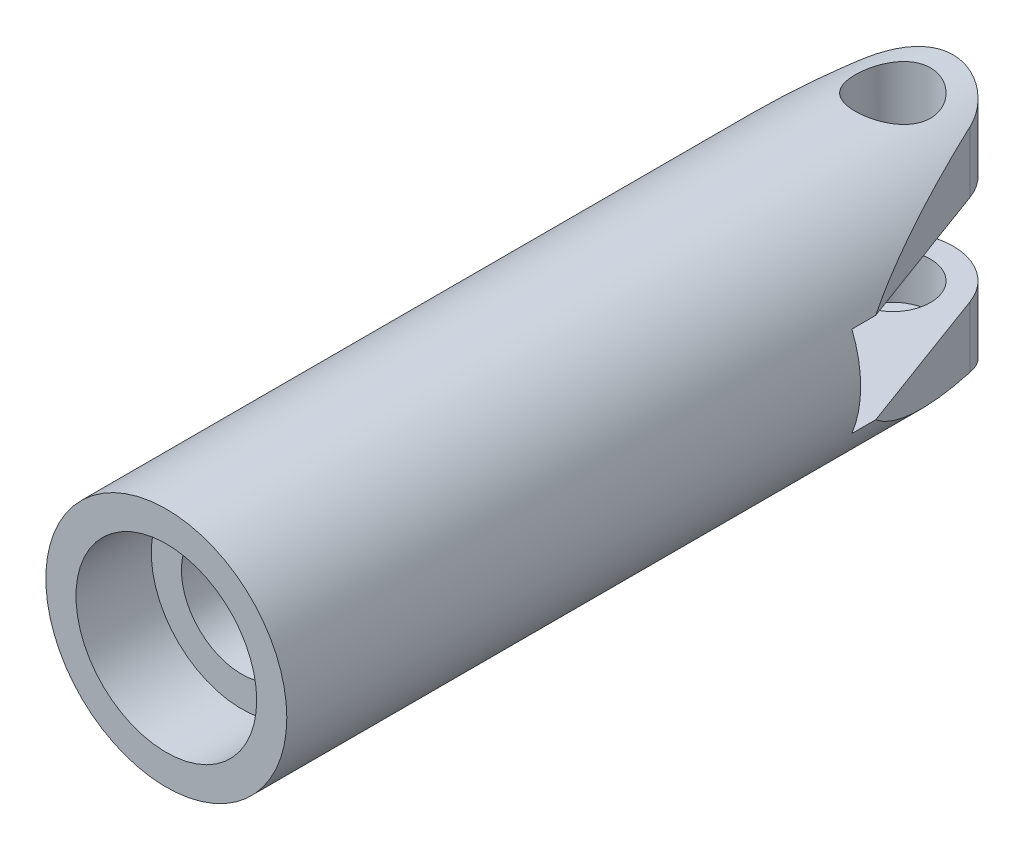
SolidWorks part; units mm, degrees
note: The reader was unsure of these and kept them because the rebuilt part matched: shared geometry of "Sketch3<4>".
ref_plane "Front" through (0, 0, 0) normal (0, 0, 1) x (1, 0, 0)
ref_plane "Top" through (0, 0, 0) normal (0, 1, 0) x (1, 0, 0)
ref_plane "Right" through (0, 0, 0) normal (1, 0, 0) x (0, 0, -1)
sketch "Sketch2" plane through (0, 0, 0) normal (1, 0, 0) x (0, 0, -1)
  line L0 (-12.9752, 0) -> (14.864, 0) construction
  line L1 (-33.1, 4) -> (0, 4)
  line L2 (0, 4) -> (0, 3)
  line L3 (0, 3) -> (20, 3)
  line L4 (20, 3) -> (20, 8)
  line L5 (20, 8) -> (-38.1, 8)
  line L6 (-38.1, 8) -> (-38.1, 6)
  line L7 (-38.1, 6) -> (-33.1, 6)
  line L8 (-33.1, 6) -> (-33.1, 4)
  dimension "D1" = 4
  dimension "D2" = 3
  dimension "D3" = 20
  dimension "D4" = 38.1
  dimension "D5" = 8
  dimension "D6" = 2
  dimension "D7" = 5
revolve "Revolve1" add sketch "Sketch2" angle 360 about L0
sketch "Sketch3" plane through (0, 0, 0) normal (0, 1, 0) x (1, 0, 0)
  line L0 (8, 25) -> (-8, 25)
  line L1 (24.9668, 0) -> (-18.1253, 0) construction
  line L4 (-8, 25) -> (-8, 0)
  line L5 (8, 25) -> (8, 0)
  line L6 (-8, -14.3434) -> (-8, 9.482) construction
  line L7 (-8, 20) -> (-8, -38.1) construction
  line L8 (8, 9.482) -> (8, -15.7471) construction
  line L9 (0, 34.4612) -> (0, -14.3434) construction
  line L14 (-3.7531, 11.5195) -> (-8, 0)
  line L15 (3.7531, 11.5195) -> (8, 0)
  arc A0 (2.1944, 11.3336) -> (-2.2419, 11.2422) centre (0, 10.1359) ccw
  circle A1 centre (0, 10.1359) radius 2.5
  circle A2 centre (0, 10.1359) radius 5.5 construction
  circle A3 centre (0, 10.1359) radius 4
  dimension "D2" = 5
  dimension "D4" = 2.5
  dimension "D1" = 25
  dimension "D3" = 16
extrude "Cut-Extrude2" cut sketch "Sketch3" against normal through all both and the other way through all
sketch "Sketch4" plane through (0, 0, 0) normal (1, 0, 0) x (0, 0, -1)
  line L0 (12.5056, 0) -> (0, 0) construction
  line L1 (25.0111, -3) -> (0, -3)
  line L2 (25.0111, -3) -> (25.0111, 3)
  line L3 (25.0111, 3) -> (0, 3)
  line L4 (0, -3) -> (0, 3)
  line L5 (25.0111, -3) -> (0, 3) construction
  line L6 (25.0111, 3) -> (0, -3) construction
  point P0 (12.5056, 0)
  dimension "D1" = 0
  dimension "D2" = 6
extrude "Cut-Extrude3" cut sketch "Sketch4" against normal through all both and the other way through all
extrude "Cut-Extrude4" cut sketch "Sketch3<4>" along normal through all and the other way blind 6 contours A1
sketch "Sketch3<4>" plane through (0, 0, 0) normal (0, 1, 0) x (1, 0, 0) same geometry as "Sketch3"
